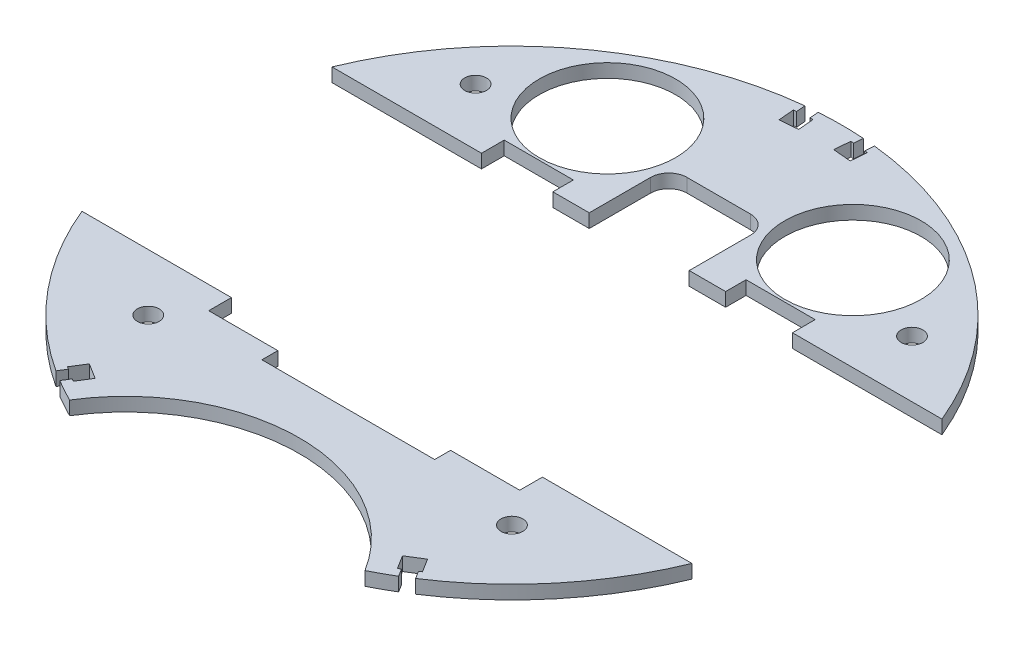
SolidWorks part; units mm, degrees
material "ABS"
ref_plane "Front Plane" through (0, 0, 0) normal (0, 0, 1) x (1, 0, 0)
ref_plane "Top Plane" through (0, 0, 0) normal (0, 1, 0) x (1, 0, 0)
ref_plane "Right Plane" through (0, 0, 0) normal (1, 0, 0) x (0, 0, -1)
sketch "Sketch1" plane through (0, 0, 0) normal (0, 1, 0) x (1, 0, 0)
  line L0 (0, -85) -> (-32.4891, -64.8129) construction
  line L1 (0, -85) -> (0, 0) construction
  arc A0 (32.4891, -64.8129) -> (-32.4891, -64.8129) centre (0, 0) ccw
  arc A1 (32.4891, -64.8129) -> (-32.4891, -64.8129) centre (0, -85) ccw
  dimension "D1" = 145
  dimension "D2" = 76.5
  dimension "D3" = 85
extrude "Boss-Extrude1" add sketch "Sketch1" along normal blind 3
sketch "solenoid placement" plane through (0, 3, 0) normal (0, 1, 0) x (1, 0, 0)
  line L4 (-19, -36) -> (19, -36)
  line L5 (-19, -36) -> (19, -36)
  line L6 (19, -36) -> (19, 28)
  line L7 (19, -36) -> (19, 28)
  line L8 (19, 28) -> (-19, 28)
  line L9 (19, 28) -> (-19, 28)
  line L10 (-19, 28) -> (-19, -36)
  line L11 (-19, 28) -> (-19, -36)
  circle A1 centre (0, 0) radius 72.5 construction
  arc A2 (32.4891, -64.8129) -> (-32.4891, -64.8129) centre (0, 0) ccw construction
  dimension "D1" = 0
extrude "Cut-Extrude1" cut sketch "solenoid placement" against normal through all
sketch "Sketch3" plane through (0, 3, 0) normal (0, 1, 0) x (1, 0, 0)
  circle A1 centre (27, 48) radius 12
  circle A2 centre (-27, 48) radius 12
  dimension "D1" = 24
extrude "Cut-Extrude3" cut sketch "Sketch3" against normal through all
sketch "Sketch4" plane through (0, 3, 0) normal (0, 1, 0) x (1, 0, 0)
  circle A2 centre (40, -40) radius 2.4
  circle A3 centre (40, -40) radius 2.4
  circle A4 centre (-40, -40) radius 2.4
  circle A5 centre (-40, -40) radius 2.4
  circle A6 centre (48, 40) radius 2.4
  circle A7 centre (48, 40) radius 2.4
  circle A8 centre (-48, 40) radius 2.4
  circle A12 centre (-48, 40) radius 2.4
  dimension "D1" = 0
  dimension "D2" = 0
  dimension "D3" = 0
  dimension "D4" = 0
extrude "Cut-Extrude4" cut sketch "Sketch4" against normal through all
sketch "Sketch2" plane through (0, 3, 0) normal (0, 1, 0) x (1, 0, 0)
  line L0 (0, 0) -> (0, 72.5) construction
  line L1 (34.2, -27.5) -> (34.2, -32.5)
  line L2 (67.082, -27.5) -> (34.2, -27.5)
  line L3 (34.2, 27.5) -> (67.082, 27.5)
  line L4 (34.2, 32.5) -> (34.2, 27.5)
  line L5 (22.2, 32.5) -> (34.2, 32.5)
  line L6 (19, 32.5) -> (22.2, 32.5)
  line L7 (19, -32.5) -> (19, 32.5)
  line L8 (22.2, -32.5) -> (19, -32.5)
  line L9 (-34.2, -32.5) -> (-22.2, -32.5)
  line L10 (-22.2, -32.5) -> (-19, -32.5)
  line L11 (-19, -32.5) -> (-19, 32.5)
  line L12 (-19, 32.5) -> (-22.2, 32.5)
  line L13 (-22.2, 32.5) -> (-34.2, 32.5)
  line L14 (-34.2, 32.5) -> (-34.2, 25)
  line L15 (-34.2, 25) -> (-68.0533, 25)
  line L16 (-68.0533, -25) -> (-34.2, -25)
  line L17 (-34.2, -25) -> (-34.2, -32.5)
  line L18 (-34.2, -32.5) -> (-22.2, -32.5)
  line L19 (-22.2, -32.5) -> (-19, -32.5)
  line L20 (-19, -32.5) -> (-19, 32.5)
  line L21 (-19, 32.5) -> (-22.2, 32.5)
  line L22 (-22.2, 32.5) -> (-34.2, 32.5)
  line L23 (-34.2, 32.5) -> (-34.2, 27.5)
  line L24 (-34.2, 27.5) -> (-67.082, 27.5)
  line L25 (-67.082, -27.5) -> (-34.2, -27.5)
  line L26 (-34.2, -27.5) -> (-34.2, -32.5)
  line L27 (34.2, -32.5) -> (22.2, -32.5)
  arc A0 (32.4891, -64.8129) -> (-32.4891, -64.8129) centre (0, 0) ccw construction
  arc A1 (67.082, 27.5) -> (67.082, -27.5) centre (0, 0) cw
  arc A2 (-68.0533, 25) -> (-68.0533, -25) centre (0, 0) ccw
  arc A3 (-67.082, 27.5) -> (-67.082, -27.5) centre (0, 0) ccw
  dimension "D2" = 55
  dimension "D1" = 0
extrude "Cut-Extrude2" cut sketch "Sketch2" against normal through all
sketch "Sketch5" plane through (0, 3, 0) normal (0, 1, 0) x (1, 0, 0)
  line L8 (-11, 28) -> (11, 28)
  line L9 (11, 28) -> (11, 41.5)
  line L10 (7, 45.5) -> (-7, 45.5)
  line L11 (-11, 41.5) -> (-11, 28)
  line L12 (19, 28) -> (-19, 28) construction
  arc A4 (11, 41.5) -> (7, 45.5) centre (7, 41.5) ccw
  arc A5 (-7, 45.5) -> (-11, 41.5) centre (-7, 41.5) ccw
  point P10 (0, 28)
  point P13 (0, 28)
  line M18 (-19, 28) -> (19, 28)
  dimension "D3" = 4
  dimension "D1" = 22
  dimension "D2" = 17.5
extrude "Cut-Extrude5" cut sketch "Sketch5" against normal through all contours L10 A5 L11 L9 A4 M18 region at (0, 3, -36.6073)
sketch "Sketch6" plane through (0, 3, 0) normal (0, 1, 0) x (-1, 0, 0)
  circle A1 centre (-27, -48) radius 15
  circle A2 centre (-27, -48) radius 15
  circle A3 centre (27, -48) radius 15
  circle A4 centre (27, -48) radius 15
  dimension "D1" = 0
  dimension "D2" = 0
extrude "Cut-Extrude10" cut sketch "Sketch6" against normal through all
sketch "Sketch7" plane through (0, 3, 0) normal (0, 1, 0) x (1, 0, 0)
  line L8 (-7.4893, 70.1141) -> (-8.1369, 70.0574)
  line L9 (-8.1369, 70.0574) -> (-7.8318, 66.5707)
  line L10 (-7.8318, 66.5707) -> (-3.847, 66.9194)
  line L11 (-3.847, 66.9194) -> (-4.1521, 70.406)
  line L12 (-4.1521, 70.406) -> (-4.7996, 70.3494)
  line L13 (-4.7996, 70.3494) -> (-4.9739, 72.3418)
  line L14 (-4.9739, 72.3418) -> (-7.6637, 72.1065)
  line L15 (-7.6637, 72.1065) -> (-7.4893, 70.1141)
  line L16 (-7.4893, 70.1141) -> (-8.1369, 70.0574)
  line L17 (-8.1369, 70.0574) -> (-7.8318, 66.5707)
  line L18 (-7.8318, 66.5707) -> (-3.847, 66.9194)
  line L19 (-3.847, 66.9194) -> (-4.1521, 70.406)
  line L20 (-4.1521, 70.406) -> (-4.7996, 70.3494)
  line L21 (-4.7996, 70.3494) -> (-4.9739, 72.3418)
  line L22 (-4.9739, 72.3418) -> (-7.6637, 72.1065)
  line L23 (-7.6637, 72.1065) -> (-7.4893, 70.1141)
  line L24 (8.1369, 70.0574) -> (7.4893, 70.1141)
  line L25 (7.8318, 66.5707) -> (8.1369, 70.0574)
  line L26 (3.847, 66.9194) -> (7.8318, 66.5707)
  line L27 (4.1521, 70.406) -> (3.847, 66.9194)
  line L28 (4.7996, 70.3494) -> (4.1521, 70.406)
  line L29 (4.9739, 72.3418) -> (4.7996, 70.3494)
  line L30 (7.6637, 72.1065) -> (4.9739, 72.3418)
  line L31 (7.4893, 70.1141) -> (7.6637, 72.1065)
  line L32 (8.1369, 70.0574) -> (7.4893, 70.1141)
  line L33 (7.8318, 66.5707) -> (8.1369, 70.0574)
  line L34 (3.847, 66.9194) -> (7.8318, 66.5707)
  line L35 (4.1521, 70.406) -> (3.847, 66.9194)
  line L36 (4.7996, 70.3494) -> (4.1521, 70.406)
  line L37 (4.9739, 72.3418) -> (4.7996, 70.3494)
  line L38 (7.6637, 72.1065) -> (4.9739, 72.3418)
  line L39 (7.4893, 70.1141) -> (7.6637, 72.1065)
  line L40 (38.5042, -59.072) -> (39.0554, -58.7276)
  line L41 (39.564, -60.7681) -> (38.5042, -59.072)
  line L42 (37.2743, -62.1989) -> (39.564, -60.7681)
  line L43 (36.2144, -60.5028) -> (37.2743, -62.1989)
  line L44 (35.6632, -60.8472) -> (36.2144, -60.5028)
  line L45 (33.8085, -57.8791) -> (35.6632, -60.8472)
  line L46 (37.2007, -55.7594) -> (33.8085, -57.8791)
  line L47 (39.0554, -58.7276) -> (37.2007, -55.7594)
  line L48 (38.5042, -59.072) -> (39.0554, -58.7276)
  line L49 (39.564, -60.7681) -> (38.5042, -59.072)
  line L50 (37.2743, -62.1989) -> (39.564, -60.7681)
  line L51 (36.2144, -60.5028) -> (37.2743, -62.1989)
  line L52 (35.6632, -60.8472) -> (36.2144, -60.5028)
  line L53 (33.8085, -57.8791) -> (35.6632, -60.8472)
  line L54 (37.2007, -55.7594) -> (33.8085, -57.8791)
  line L55 (39.0554, -58.7276) -> (37.2007, -55.7594)
  line L56 (-39.0554, -58.7276) -> (-38.5042, -59.072)
  line L57 (-37.2007, -55.7594) -> (-39.0554, -58.7276)
  line L58 (-33.8085, -57.8791) -> (-37.2007, -55.7594)
  line L59 (-35.6632, -60.8472) -> (-33.8085, -57.8791)
  line L60 (-36.2144, -60.5028) -> (-35.6632, -60.8472)
  line L61 (-37.2743, -62.1989) -> (-36.2144, -60.5028)
  line L62 (-39.564, -60.7681) -> (-37.2743, -62.1989)
  line L63 (-38.5042, -59.072) -> (-39.564, -60.7681)
  line L64 (-39.0554, -58.7276) -> (-38.5042, -59.072)
  line L65 (-37.2007, -55.7594) -> (-39.0554, -58.7276)
  line L66 (-33.8085, -57.8791) -> (-37.2007, -55.7594)
  line L67 (-35.6632, -60.8472) -> (-33.8085, -57.8791)
  line L68 (-36.2144, -60.5028) -> (-35.6632, -60.8472)
  line L69 (-37.2743, -62.1989) -> (-36.2144, -60.5028)
  line L70 (-39.564, -60.7681) -> (-37.2743, -62.1989)
  line L71 (-38.5042, -59.072) -> (-39.564, -60.7681)
  dimension "D1" = 0
  dimension "D2" = 0
  dimension "D3" = 0
  dimension "D4" = 0
extrude "Cut-Extrude11" cut sketch "Sketch7" against normal through all
equation "\"smallPulleyTeeth\"= 30"
equation "\"largePulleyTeeth\"= 30"
equation "\"eighthThick\"= 3.0mm"
equation "\"sixteenthThick\" = 1.7mm"
equation "\"quarterThick\"=6.0mm"
equation "\"OD\" = 145mm"
equation "\"puckAngle\" = 60.5deg"
equation "\"D1@Sketch1\"=\"OD\""
equation "\"puckDiam\" = 76.5mm"
equation "\"D2@Sketch1\"=\"puckDiam\""
equation "\"D1@Boss-Extrude1\"=\"eighthThick\""
equation "\"axlePress\" = 5.9mm"
equation "\"press\" = 0.2mm"
equation "\"wheelClear\" = 0.3mm"
equation "\"10-32clear\" = 4.8mm"
equation "\"6-32clear\" = 3.3mm"
equation "\"8-32clear\" = 4.0mm"
equation "\"wheelHeight\" = 22mm"
equation "\"wheelWell\" = 65mm"
equation "\"puckDist\" = 85mm"
equation "\"scoopFillet\" = 5mm"
equation "\"4-40clear\" = 3.0mm"
equation "\"D3@Sketch1\"=\"puckDist\""
